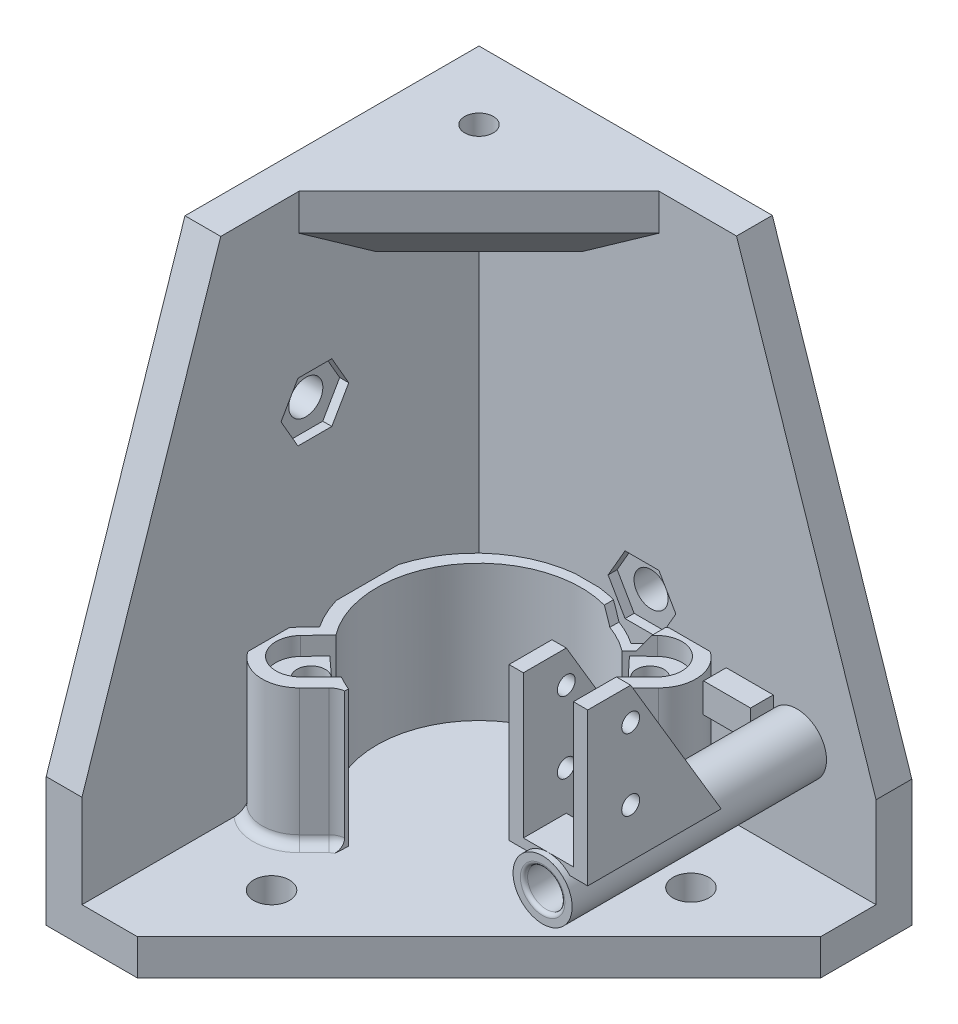
SolidWorks part; units mm, degrees
ref_plane "Front" through (0, 0, 0) normal (0, 0, 1) x (1, 0, 0)
ref_plane "Top" through (0, 0, 0) normal (0, 1, 0) x (1, 0, 0)
ref_plane "Right" through (0, 0, 0) normal (1, 0, 0) x (0, 0, -1)
sketch "Sketch1" plane through (0, 0, 0) normal (0, 1, 0) x (1, 0, 0)
  line L0 (0, 0) -> (0, 60.5)
  line L1 (0, -55) -> (0, 55) construction
  line L2 (0, 60.5) -> (60.5, 60.5)
  line L3 (60.5, 60.5) -> (60.5, 47.75)
  line L4 (60.5, 47.75) -> (12.75, 0)
  line L5 (-55, 0) -> (55, 0) construction
  line L6 (12.75, 0) -> (0, 0)
  dimension "D1" = 60.5
  dimension "D2" = 12.75
extrude "Boss-Extrude1" add sketch "Sketch1" along normal blind 5
sketch "Sketch4" plane through (0, 0, 0) normal (-1, 0, 0) x (0, 0, 1)
  line L0 (-60.5, 5) -> (-60.5, 76.1962)
  line L1 (-60.5, 76.1962) -> (-19.4, 76.1962)
  line L2 (-19.4, 76.1962) -> (0, 18.0048)
  line L3 (0, 18.0048) -> (0, 5)
  line L4 (0, -2.75) -> (0, 2.75) construction
  line L5 (-60.5, 5) -> (0, 5) construction
  line L6 (-60.5, 5) -> (0, 5)
  dimension "D1" = 71.1962
  dimension "D2" = 41.1
  dimension "D3" = 61.34
extrude "Boss-Extrude2" add sketch "Sketch4" against normal blind 5
sketch "Sketch5" plane through (0, 0, -60.5) normal (0, 0, -1) x (-1, 0, 0)
  line L0 (0, 76.1962) -> (-41, 76.1962)
  line L1 (-41, 76.1962) -> (-60.5, 17.7009)
  line L2 (-60.5, 17.7009) -> (-60.5, 5)
  line L6 (-60.5, 0) -> (0, 0)
  line L7 (0, 0) -> (0, 76.1962)
  line L8 (0, 76.1962) -> (-5, 76.1962)
  line L9 (-5, 76.1962) -> (-5, 5)
  line L10 (-5, 5) -> (-60.5, 5)
  line L11 (-60.5, 5) -> (-60.5, 0)
  line L12 (-60.5, 0) -> (0, 0)
  line L13 (0, 0) -> (0, 76.1962)
  line L14 (0, 76.1962) -> (-5, 76.1962)
  line L15 (-5, 76.1962) -> (-5, 5)
  line L16 (-5, 5) -> (-60.5, 5)
  line L17 (-60.5, 5) -> (-60.5, 0)
  line M13 (-5, 76.1962) -> (-5, 5)
  line M14 (-5, 5) -> (-60.5, 5)
  dimension "D2" = 41
  dimension "D3" = 61.66
  dimension "D1" = 0
extrude "Boss-Extrude3" add sketch "Sketch5" against normal blind 5 contours L1 L2 L0 M14 M13 region at (29.1655, 37.8824, -60.5)
sketch "Sketch6" plane through (0, 5, 0) normal (0, 1, 0) x (1, 0, 0)
  line L0 (60.5, 60.5) -> (0, 60.5) construction
  line L4 (0, 19.4) -> (0, 0)
  line L5 (60.5, 55.5) -> (5, 55.5)
  line L6 (5, 55.5) -> (5, 0)
  line L7 (5, 0) -> (12.75, 0)
  line L8 (12.75, 0) -> (60.5, 47.75)
  line L9 (60.5, 47.75) -> (60.5, 55.5)
  line L10 (60.5, 55.5) -> (5, 55.5)
  line L11 (5, 55.5) -> (5, 0)
  line L12 (5, 0) -> (12.75, 0)
  line L13 (12.75, 0) -> (60.5, 47.75)
  line L14 (60.5, 47.75) -> (60.5, 55.5)
  line L15 (0, 0) -> (5, 0)
  line L16 (5, 0) -> (5, 19.4)
  line L17 (5, 19.4) -> (0, 19.4)
  line L18 (0, 19.4) -> (0, 0)
  line L19 (0, 0) -> (5, 0)
  line L20 (5, 0) -> (5, 19.4)
  line L21 (5, 19.4) -> (0, 19.4)
  line L24 (0, 60.5) -> (0, 19.4)
  line L25 (0, 19.4) -> (5, 19.4)
  line L26 (5, 19.4) -> (5, 55.5)
  line L27 (5, 55.5) -> (41, 55.5)
  line L28 (41, 55.5) -> (41, 60.5)
  line L29 (41, 60.5) -> (0, 60.5)
  line L30 (0, 60.5) -> (0, 19.4)
  line L31 (0, 19.4) -> (5, 19.4)
  line L32 (5, 19.4) -> (5, 55.5)
  line L33 (5, 55.5) -> (41, 55.5)
  line L34 (41, 55.5) -> (41, 60.5)
  line L35 (41, 60.5) -> (0, 60.5)
  circle A0 centre (16.5, 15) radius 2.5
  circle A1 centre (45.5, 44.625) radius 2.5
  dimension "D1" = 5
  dimension "D2" = 5
  dimension "D3" = 0
  dimension "D4" = 15
  dimension "D6" = 16.5
  dimension "D7" = 15
  dimension "D9" = 15.875
  dimension "D5" = 0
  dimension "D8" = 0
extrude "Cut-Extrude1" cut sketch "Sketch6" against normal through all contours A0 | A1 region at (16.5, 5, -15) region at (45.5, 5, -44.625)
sketch "Sketch9" plane through (0, 0, -55.5) normal (0, 0, 1) x (1, 0, 0)
  line L1 (5, 76.1962) -> (5, 5) construction
  line L5 (0, 0) -> (60.5, 0)
  line L6 (0, 76.1962) -> (0, 0)
  line L7 (41, 76.1962) -> (0, 76.1962)
  line L8 (60.5, 17.7009) -> (41, 76.1962)
  line L9 (60.5, 0) -> (60.5, 17.7009)
  line L10 (0, 0) -> (60.5, 0)
  line L11 (0, 76.1962) -> (0, 0)
  line L12 (41, 76.1962) -> (0, 76.1962)
  line L13 (60.5, 17.7009) -> (41, 76.1962)
  line L14 (60.5, 0) -> (60.5, 17.7009)
  line L15 (49.45, 19.0462) -> (49.45, 3.6199) construction
  circle A0 centre (49.45, 19.0462) radius 4.1275
  circle A1 centre (49.45, 19.0462) radius 2.6035
  dimension "D2" = 5.207
  dimension "D3" = 1.524
  dimension "D4" = 57.15
  dimension "D5" = 44.45
  dimension "D1" = 0
extrude "Boss-Extrude5" add sketch "Sketch9" along normal blind 35.56 contours A1 A0 region at (45.4392, 19.0462, -55.5)
fillet "Fillet1" radius 0.508 1 edges at (52.0535, 19.0462, -19.94)
sketch "Sketch14" plane through (0, 5, 0) normal (0, 1, 0) x (1, 0, 0)
  line L0 (13.4627, 27.5396) -> (14.7681, 26.7924)
  line L1 (12.75, 0) -> (60.5, 47.75) construction
  line L2 (36.625, 23.875) -> (5, 55.5) construction
  line L3 (5, 55.5) -> (60.5, 55.5) construction
  line L4 (32.9604, 47.0373) -> (33.7076, 45.7319)
  line L5 (14.8281, 26.8523) -> (11.8274, 23.8516)
  line L6 (6.723, 28.8027) -> (9.1327, 31.3641)
  line L7 (33.6477, 45.6719) -> (36.6484, 48.6726)
  line L8 (31.6973, 53.777) -> (29.1359, 51.3673)
  line L9 (15.0744, 24.4582) -> (13.006, 22.3898)
  line L10 (5.6561, 29.7396) -> (7.0609, 31.1444)
  line L11 (36.0418, 45.4256) -> (38.1102, 47.494)
  line L12 (30.7604, 54.8439) -> (28.83, 52.9135)
  line L13 (18.1324, 24.8665) -> (30.5234, 17.7734)
  line L14 (35.6335, 42.3676) -> (42.7266, 29.9766)
  line L15 (31.7409, 18.9909) -> (18.852, 25.7543)
  line L16 (41.5091, 28.7591) -> (34.7457, 41.648)
  line L17 (16.5689, 25.6946) -> (16.5343, 25.1798)
  line L18 (34.7457, 41.648) -> (35.7996, 42.0774)
  circle A0 centre (20.5607, 39.9393) radius 14.2875
  arc A1 (11.8274, 23.8516) -> (6.723, 28.8027) centre (9.3129, 26.3661) cw
  arc A2 (36.6484, 48.6726) -> (31.6973, 53.777) centre (34.1339, 51.1871) ccw
  arc A3 (13.006, 22.3898) -> (5.6561, 29.7396) centre (9.3311, 26.0647) cw
  arc A4 (38.1102, 47.494) -> (30.7604, 54.8439) centre (34.4353, 51.1689) ccw
  arc A5 (7.0609, 31.1444) -> (28.83, 52.9135) centre (20.0709, 39.9035) cw
  arc A6 (36.0418, 45.4256) -> (35.6335, 42.3676) centre (37.8378, 43.6295) ccw
  arc A7 (15.0744, 24.4582) -> (18.1324, 24.8665) centre (16.8705, 22.6622) cw
  arc A9 (33.8602, 45.8844) -> (36.3595, 38.5726) centre (13.6025, 34.877) cw
  arc A10 (14.6156, 26.6398) -> (21.9274, 24.1405) centre (25.623, 46.8975) ccw
  point P40 (34.6689, 44.0527)
  point P43 (16.4473, 25.8311)
  line M13 (60.5, 55.5) -> (5, 55.5)
  line M14 (5, 55.5) -> (5, 0)
  line M16 (12.75, 0) -> (60.5, 47.75)
  dimension "D1" = 28.575
  dimension "D2" = 3.556
  dimension "D3" = 2.54
extrude "Boss-Extrude6" add sketch "Sketch14" along normal blind 19.05 contours L2 A0 L5 A1 L6 A5 L10 A3 L9 A7 L13 M16 M14 | L2 L14 A6 L11 A4 L12 A5 A0 L8 A2 L7 M16 M13 region at (7.691, 5, -30.3062) region at (10.0875, 5, -50.8829)
sketch "Sketch15" plane through (0, 76.1962, 0) normal (0, 1, 0) x (1, 0, 0)
  line L0 (5, 30.3375) -> (30.1625, 55.5)
  line L1 (0, -33.275) -> (0, 33.275) construction
  line L2 (41, 60.5) -> (0, 60.5) construction
  line L6 (0, 60.5) -> (0, 19.4)
  line L7 (0, 19.4) -> (5, 19.4)
  line L8 (5, 19.4) -> (5, 55.5)
  line L9 (5, 55.5) -> (41, 55.5)
  line L10 (41, 55.5) -> (41, 60.5)
  line L11 (41, 60.5) -> (0, 60.5)
  line L13 (0, 19.4) -> (5, 19.4)
  line L14 (5, 30.3375) -> (5, 55.5)
  line L15 (5, 55.5) -> (30.1625, 55.5)
  line L16 (41, 55.5) -> (41, 60.5)
  circle A0 centre (9.525, 50.975) radius 2
  line M11 (5, 19.4) -> (5, 55.5)
  line M12 (5, 55.5) -> (41, 55.5)
  dimension "D3" = 4
  dimension "D4" = 9.525
  dimension "D5" = 9.525
  dimension "D2" = 45
  dimension "D1" = 0
extrude "Boss-Extrude7" add sketch "Sketch15" against normal blind 12.7 contours L0 A0 M11 M12 region at (13.5472, 76.1962, -46.9528)
chamfer "Chamfer2" distance 7.62 angle 45 1 edges at (17.5813, 63.4962, -42.9187)
fillet "Fillet2" radius 1.27 7 edges at (39.6065, 5, -51.6871) (37.076, 5, -46.4598) (35.3202, 5, -43.9657) (8.8129, 5, -20.8935) (14.0402, 5, -23.424) (15.745, 5, -24.9392) (35.7165, 5, -42.2225)
sketch "Sketch16" plane through (0, 0, -55.5) normal (0, 0, 1) x (1, 0, 0)
  line L1 (46.1305, 23.2107) -> (38.2864, 23.2107)
  line L2 (46.1305, 23.2107) -> (46.1305, 19.0978)
  line L3 (46.1305, 19.0978) -> (38.2864, 19.0978)
  line L4 (38.2864, 23.2107) -> (38.2864, 19.0978)
extrude "Boss-Extrude8" add sketch "Sketch16" along normal blind 3.175
chamfer "Chamfer3" distance 1.27 angle 45 1 edges at (38.2864, 23.2107, -55.0794)
sketch "Sketch17" plane through (0, 5, 0) normal (0, 1, 0) x (1, 0, 0)
  line L0 (8.716, 30.9212) -> (14.047, 26.0712)
  line L1 (36.625, 23.875) -> (5, 55.5) construction
  line L2 (12.75, 0) -> (60.5, 47.75) construction
  line L3 (5, 55.5) -> (18.418, 55.5) construction
  line L4 (5, 55.5) -> (5, 44.2452) construction
  line L5 (29.6632, 51.8634) -> (34.5959, 46.6202)
  line L22 (37.3079, 55.5) -> (31.5627, 55.5)
  line L23 (30.7604, 54.8439) -> (28.83, 52.9135)
  line L24 (21.7238, 55.5) -> (18.418, 55.5)
  line L25 (5, 44.2452) -> (5, 35.5618)
  line L26 (7.0609, 31.1444) -> (5.6561, 29.7396)
  line L27 (5, 28.9373) -> (5, 23.1921)
  line L28 (13.006, 22.3898) -> (15.0744, 24.4582)
  line L29 (16.5343, 25.1798) -> (16.5689, 25.6946)
  line L30 (16.5343, 25.1798) -> (16.5689, 25.6946)
  line L31 (35.539, 41.9712) -> (35.7996, 42.0774)
  line L32 (35.539, 41.9712) -> (35.7996, 42.0774)
  line L33 (14.6156, 26.6398) -> (11.8274, 23.8516)
  line L34 (6.723, 28.8027) -> (9.1327, 31.3641)
  line L35 (29.1359, 51.3673) -> (31.6973, 53.777)
  line L36 (36.6484, 48.6726) -> (33.8602, 45.8844)
  line L40 (35.7996, 42.0774) -> (35.6335, 42.3676)
  line L41 (36.0418, 45.4256) -> (38.1102, 47.494)
  line L43 (37.3079, 55.5) -> (31.5627, 55.5)
  line L44 (30.7604, 54.8439) -> (28.83, 52.9135)
  line L45 (21.7238, 55.5) -> (18.418, 55.5)
  line L46 (5, 44.2452) -> (5, 35.5618)
  line L47 (7.0609, 31.1444) -> (5.6561, 29.7396)
  line L48 (5, 28.9373) -> (5, 23.1921)
  line L49 (13.006, 22.3898) -> (15.0744, 24.4582)
  line L54 (14.6156, 26.6398) -> (11.8274, 23.8516)
  line L55 (6.723, 28.8027) -> (9.1327, 31.3641)
  line L56 (29.1359, 51.3673) -> (31.6973, 53.777)
  line L57 (36.6484, 48.6726) -> (33.8602, 45.8844)
  line L61 (35.7996, 42.0774) -> (35.6335, 42.3676)
  line L62 (36.0418, 45.4256) -> (38.1102, 47.494)
  circle A1 centre (33.6908, 50.7324) radius 2.1828
  circle A2 centre (10.0204, 27.0078) radius 1.9844
  circle A3 centre (33.6908, 50.7324) radius 1.9288
  arc A15 (38.1102, 47.494) -> (37.3079, 55.5) centre (34.4353, 51.1689) ccw
  arc A17 (31.5627, 55.5) -> (30.7604, 54.8439) centre (34.4353, 51.1689) ccw
  arc A18 (28.83, 52.9135) -> (21.7238, 55.5) centre (20.0709, 39.9035) ccw
  arc A19 (18.418, 55.5) -> (5, 44.2452) centre (20.0709, 39.9035) ccw
  arc A20 (5, 35.5618) -> (7.0609, 31.1444) centre (20.0709, 39.9035) ccw
  arc A21 (5.6561, 29.7396) -> (5, 28.9373) centre (9.3311, 26.0647) ccw
  arc A22 (5, 23.1921) -> (13.006, 22.3898) centre (9.3311, 26.0647) ccw
  arc A23 (16.5343, 25.1798) -> (15.0744, 24.4582) centre (16.8705, 22.6622) ccw
  arc A24 (14.6156, 26.6398) -> (16.5689, 25.6946) centre (25.623, 46.8975) ccw
  arc A25 (6.723, 28.8027) -> (11.8274, 23.8516) centre (9.3129, 26.3661) ccw
  arc A26 (29.1359, 51.3673) -> (9.1327, 31.3641) centre (20.5607, 39.9393) ccw
  arc A27 (36.6484, 48.6726) -> (31.6973, 53.777) centre (34.1339, 51.1871) ccw
  arc A28 (35.539, 41.9712) -> (33.8602, 45.8844) centre (13.6025, 34.877) ccw
  arc A29 (36.0418, 45.4256) -> (35.6335, 42.3676) centre (37.8378, 43.6295) ccw
  arc A30 (38.1102, 47.494) -> (37.3079, 55.5) centre (34.4353, 51.1689) ccw
  arc A32 (31.5627, 55.5) -> (30.7604, 54.8439) centre (34.4353, 51.1689) ccw
  arc A33 (28.83, 52.9135) -> (21.7238, 55.5) centre (20.0709, 39.9035) ccw
  arc A34 (18.418, 55.5) -> (5, 44.2452) centre (20.0709, 39.9035) ccw
  arc A35 (5, 35.5618) -> (7.0609, 31.1444) centre (20.0709, 39.9035) ccw
  arc A36 (5.6561, 29.7396) -> (5, 28.9373) centre (9.3311, 26.0647) ccw
  arc A37 (5, 23.1921) -> (13.006, 22.3898) centre (9.3311, 26.0647) ccw
  arc A38 (16.5343, 25.1798) -> (15.0744, 24.4582) centre (16.8705, 22.6622) ccw
  arc A39 (14.6156, 26.6398) -> (16.5689, 25.6946) centre (25.623, 46.8975) ccw
  arc A40 (6.723, 28.8027) -> (11.8274, 23.8516) centre (9.3129, 26.3661) ccw
  arc A41 (29.1359, 51.3673) -> (9.1327, 31.3641) centre (20.5607, 39.9393) ccw
  arc A42 (36.6484, 48.6726) -> (31.6973, 53.777) centre (34.1339, 51.1871) ccw
  arc A43 (35.539, 41.9712) -> (33.8602, 45.8844) centre (13.6025, 34.877) ccw
  arc A44 (36.0418, 45.4256) -> (35.6335, 42.3676) centre (37.8378, 43.6295) ccw
  line M44 (33.8602, 45.8844) -> (36.6484, 48.6726)
  arc M45 (36.6484, 48.6726) -> (31.6973, 53.777) centre (34.1339, 51.1871) ccw
  line M46 (31.6973, 53.777) -> (29.1359, 51.3673)
  line M48 (9.1327, 31.3641) -> (6.723, 28.8027)
  arc M49 (6.723, 28.8027) -> (11.8274, 23.8516) centre (9.3129, 26.3661) ccw
  line M50 (11.8274, 23.8516) -> (14.6156, 26.6398)
  dimension "D2" = 3.9688
  dimension "D3" = 0.254
  dimension "D1" = 0
extrude "Boss-Extrude9" add sketch "Sketch17" along normal offset from surface (16.51 mm away) 2.54 contours L5 A1 M46 M44 M45 | L0 M48 M49 M50 | A1 L5 A3 region at (11.3737, 5, -28.4876) region at (30.7585, 5, -52.737) region at (33.0584, 5, -52.7569) up to face at (20.9693, 24.05, -39.9839)
sketch "Sketch18" plane through (0, 0, 0) normal (-1, 0, 0) x (0, 0, 1)
  line L0 (-60.5, 76.1962) -> (-60.5, 0) construction
  line L1 (33.275, 0) -> (-33.275, 0) construction
  circle A0 centre (-32.56, 49.53) radius 2.3813
  dimension "D1" = 27.94
  dimension "D2" = 49.53
  dimension "D3" = 4.7625
extrude "Cut-Extrude2" cut sketch "Sketch18" against normal up to next
sketch "Sketch19" plane through (0, 0, -60.5) normal (0, 0, -1) x (-1, 0, 0)
  line L0 (0, 33.275) -> (0, -33.275) construction
  line L1 (33.275, 0) -> (-33.275, 0) construction
  circle A0 centre (-27.7812, 26.1937) radius 2.3813
  dimension "D1" = 27.7812
  dimension "D2" = 26.1937
  dimension "D3" = 4.7625
extrude "Cut-Extrude3" cut sketch "Sketch19" against normal up to next
sketch "Sketch20" plane through (0, 0, -55.5) normal (0, 0, 1) x (1, 0, 0)
  line L1 (32.5155, 26.1938) -> (30.1484, 30.2938)
  line L2 (30.1484, 30.2938) -> (25.4141, 30.2938)
  line L3 (25.4141, 30.2938) -> (23.047, 26.1938)
  line L4 (23.047, 26.1938) -> (25.4141, 22.0938)
  line L5 (25.4141, 22.0938) -> (30.1484, 22.0938)
  line L6 (30.1484, 22.0938) -> (32.5155, 26.1938)
  circle A0 centre (27.7812, 26.1937) radius 2.3813 construction
  circle A1 centre (27.7812, 26.1937) radius 2.3813
  circle A2 centre (27.7812, 26.1937) radius 4.1 construction
  dimension "D1" = 8.2
extrude "Cut-Extrude4" cut sketch "Sketch20" against normal blind 1.27 and the other way up to vertex (4.1327 mm away) contours L1 L2 L3 L4 L5 L6 other way up to point (29.1359, 24.05, -51.3673)
sketch "Sketch21" plane through (5, 0, 0) normal (1, 0, 0) x (0, 0, -1)
  line L1 (34.9271, 53.63) -> (30.1929, 53.63)
  line L2 (30.1929, 53.63) -> (27.8257, 49.53)
  line L3 (27.8257, 49.53) -> (30.1929, 45.43)
  line L4 (30.1929, 45.43) -> (34.9271, 45.43)
  line L5 (34.9271, 45.43) -> (37.2943, 49.53)
  line L6 (37.2943, 49.53) -> (34.9271, 53.63)
  circle A0 centre (32.56, 49.53) radius 2.3813 construction
  circle A1 centre (32.56, 49.53) radius 2.3812
  circle A2 centre (32.56, 49.53) radius 4.1 construction
  dimension "D1" = 8.2
extrude "Cut-Extrude5" cut sketch "Sketch21" against normal blind 1.27 contours L1 L2 L3 L4 L5 L6
sketch "Sketch23" plane through (0, 0, 0) normal (0, 1, 0) x (1, 0, 0)
  line L1 (60.5, 60.5) -> (101.14, 60.5)
  line L2 (60.5, 60.5) -> (60.5, 24.94)
  line L3 (60.5, 24.94) -> (101.14, 24.94)
  line L4 (101.14, 60.5) -> (101.14, 24.94)
  dimension "D1" = 40.64
  dimension "D2" = 35.56
extrude "Boss-Extrude12" [suppressed] add sketch "Sketch23" along normal blind 5.08
sketch "Sketch24" [suppressed] plane through (0, 5.08, 0) normal (0, 1, 0) x (1, 0, 0)
  line L0 (101.14, 60.5) -> (60.5, 60.5) construction
  line L1 (60.5, 47.75) -> (60.5, 55.5) construction
  circle A0 centre (65.58, 55.42) radius 1.7145
  circle A1 centre (96.06, 55.42) radius 1.7145
  circle A2 centre (96.06, 29.258) radius 1.7145
  circle A3 centre (65.58, 29.258) radius 1.7145
  dimension "D1" = 3.429
  dimension "D2" = 26.162
  dimension "D3" = 30.48
  dimension "D4" = 5.08
  dimension "D5" = 5.08
extrude "Cut-Extrude6" [suppressed] cut sketch "Sketch24" against normal up to next
sketch "Sketch25" plane through (0, 63.4962, 0) normal (0, -1, 0) x (1, 0, 0)
  line L1 (13.5665, -50.975) -> (11.5457, -47.475)
  line L2 (11.5457, -47.475) -> (7.5043, -47.475)
  line L3 (7.5043, -47.475) -> (5.4835, -50.975)
  line L4 (5.4835, -50.975) -> (7.5043, -54.475)
  line L5 (7.5043, -54.475) -> (11.5457, -54.475)
  line L6 (11.5457, -54.475) -> (13.5665, -50.975)
  circle A0 centre (9.525, -50.975) radius 2 construction
  circle A1 centre (9.525, -50.975) radius 2
  circle A2 centre (9.525, -50.975) radius 3.5 construction
  dimension "D1" = 7
extrude "Cut-Extrude7" cut sketch "Sketch25" against normal blind 4
ref_plane "Plane1" through (0, 23.1737, 0) normal (0, 1, 0) x (1, 0, 0)
sketch "Sketch26" plane through (0, 23.1737, 0) normal (0, 1, 0) x (1, 0, 0)
  line L0 (45.3225, 19.94) -> (53.5775, 19.94) construction
  line L1 (43.95, 26.75) -> (54.95, 26.75)
  line L2 (43.95, 26.75) -> (43.95, 20.75)
  line L3 (43.95, 20.75) -> (54.95, 20.75)
  line L4 (54.95, 26.75) -> (54.95, 20.75)
  line L5 (43.95, 26.75) -> (54.95, 20.75) construction
  line L6 (43.95, 20.75) -> (54.95, 26.75) construction
  line L7 (45.3225, 19.94) -> (53.5775, 19.94)
  line L9 (45.95, 26.75) -> (52.95, 26.75)
  line L10 (45.95, 26.75) -> (45.95, 20.75)
  line L11 (45.95, 20.75) -> (52.95, 20.75)
  line L12 (52.95, 26.75) -> (52.95, 20.75)
  line L13 (45.95, 26.75) -> (52.95, 20.75) construction
  line L14 (45.95, 20.75) -> (52.95, 26.75) construction
  point P0 (49.45, 23.75)
  point P9 (49.45, 19.94)
  point P10 (49.45, 23.75)
  dimension "D1" = 11
  dimension "D2" = 6
  dimension "D3" = 3.81
  dimension "D4" = 2
extrude "Boss-Extrude13" add sketch "Sketch26" along normal blind 20 separate body contours L10 L1 L2 L3 | L1 L12 L3 L4 region at (44.95, 23.1737, -23.75) region at (53.95, 23.1737, -23.75)
extrude "Boss-Extrude14" add sketch "Sketch26<4>" against normal blind 1.3 contours L10 L1 L2 L3 | L12 L1 L10 L3 | L1 L12 L3 L4 region at (44.95, 23.1737, -23.75) region at (49.45, 23.1737, -23.75) region at (53.95, 23.1737, -23.75)
sketch "Sketch26<4>" plane through (0, 23.1737, 0) normal (0, 1, 0) x (1, 0, 0) same geometry as "Sketch26"
sketch "Sketch27" plane through (54.95, 0, 0) normal (1, 0, 0) x (0, 0, -1)
  line L0 (26.75, 43.1737) -> (39.4036, 21.8737)
  line L1 (26.75, 21.8737) -> (39.4036, 21.8737)
  line L2 (26.75, 43.1737) -> (26.75, 21.8737)
  dimension "D1" = 12.6536
extrude "Boss-Extrude15" add sketch "Sketch27" against normal up to surface (2 mm away) from offset 0 up to face at (52.95, 33.1737, -23.75)
sketch "Sketch28" plane through (43.95, 0, 0) normal (-1, 0, 0) x (0, 0, 1)
  line L6 (-26.75, 23.1737) -> (-20.75, 23.1737)
  line L7 (-20.75, 23.1737) -> (-20.75, 43.1737)
  line L8 (-20.75, 43.1737) -> (-26.75, 43.1737)
  line L9 (-26.75, 43.1737) -> (-39.4036, 21.8737)
  line L10 (-39.4036, 21.8737) -> (-26.75, 21.8737)
  line L11 (-26.75, 21.8737) -> (-26.75, 23.1737)
  line L12 (-26.75, 23.1737) -> (-20.75, 23.1737)
  line L13 (-20.75, 23.1737) -> (-20.75, 43.1737)
  line L14 (-20.75, 43.1737) -> (-26.75, 43.1737)
  line L15 (-26.75, 43.1737) -> (-39.4036, 21.8737)
  line L16 (-39.4036, 21.8737) -> (-26.75, 21.8737)
  line L17 (-26.75, 21.8737) -> (-26.75, 23.1737)
  dimension "D1" = 0
extrude "Boss-Extrude16" add sketch "Sketch28" against normal up to surface (2 mm away) up to face at (45.95, 33.1737, -23.75)
sketch "Sketch30" plane through (52.95, 0, 0) normal (-1, 0, 0) x (0, 0, 1)
  line L6 (-26.75, 23.1737) -> (-20.75, 23.1737)
  line L7 (-20.75, 23.1737) -> (-20.75, 43.1737)
  line L8 (-20.75, 43.1737) -> (-26.75, 43.1737)
  line L9 (-26.75, 43.1737) -> (-39.4036, 21.8737)
  line L10 (-39.4036, 21.8737) -> (-26.75, 21.8737)
  line L11 (-26.75, 21.8737) -> (-26.75, 23.1737)
  line L12 (-26.75, 23.1737) -> (-20.75, 23.1737)
  line L13 (-20.75, 23.1737) -> (-20.75, 43.1737)
  line L14 (-20.75, 43.1737) -> (-26.75, 43.1737)
  line L15 (-26.75, 43.1737) -> (-39.4036, 21.8737)
  line L16 (-39.4036, 21.8737) -> (-26.75, 21.8737)
  line L17 (-26.75, 21.8737) -> (-26.75, 23.1737)
  circle A0 centre (-26.75, 28.6737) radius 1.25
  circle A1 centre (-26.75, 38.6737) radius 1.25
  dimension "D2" = 5.5
  dimension "D3" = 10
  dimension "D4" = 2.5
  dimension "D5" = 2.5
  dimension "D6" = 6
  dimension "D1" = 0
extrude "Cut-Extrude8" cut sketch "Sketch30" against normal through all and the other way up to surface (9 mm away) contours A1 | A0 region at (52.95, 28.6737, -26.75) region at (52.95, 38.6737, -26.75) other way up to face at (43.95, 32.5237, -26.9134)
